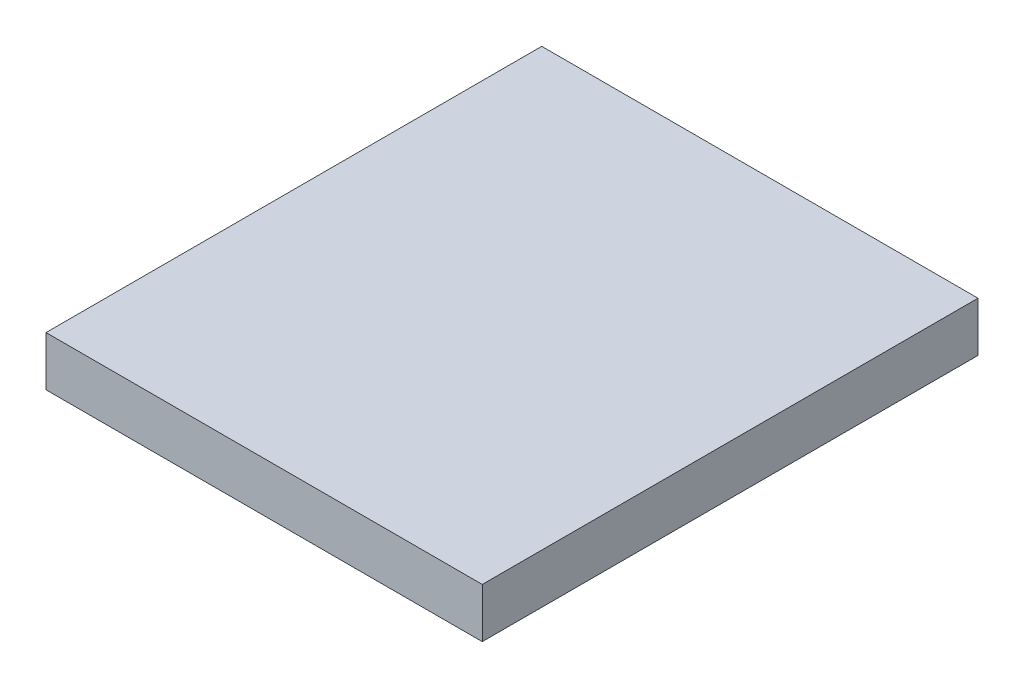
SolidWorks part; units mm, degrees
material "Oak"
ref_plane "Front Plane" through (0, 0, 0) normal (0, 0, 1) x (1, 0, 0)
ref_plane "Top Plane" through (0, 0, 0) normal (0, 1, 0) x (1, 0, 0)
ref_plane "Right Plane" through (0, 0, 0) normal (1, 0, 0) x (0, 0, -1)
sketch "Sketch1" plane through (0, 0, 0) normal (0, 1, 0) x (1, 0, 0)
  line L1 (-220, -250) -> (220, -250)
  line L2 (-220, -250) -> (-220, 250)
  line L3 (-220, 250) -> (220, 250)
  line L4 (220, -250) -> (220, 250)
  line L5 (-220, -250) -> (220, 250) construction
  line L6 (-220, 250) -> (220, -250) construction
  point P0 (0, 0)
  point P7 (0, 0)
  point P8 (0, 0)
  dimension "D1" = 500
  dimension "D2" = 440
extrude "Boss-Extrude1" add sketch "Sketch1" along normal blind 50
